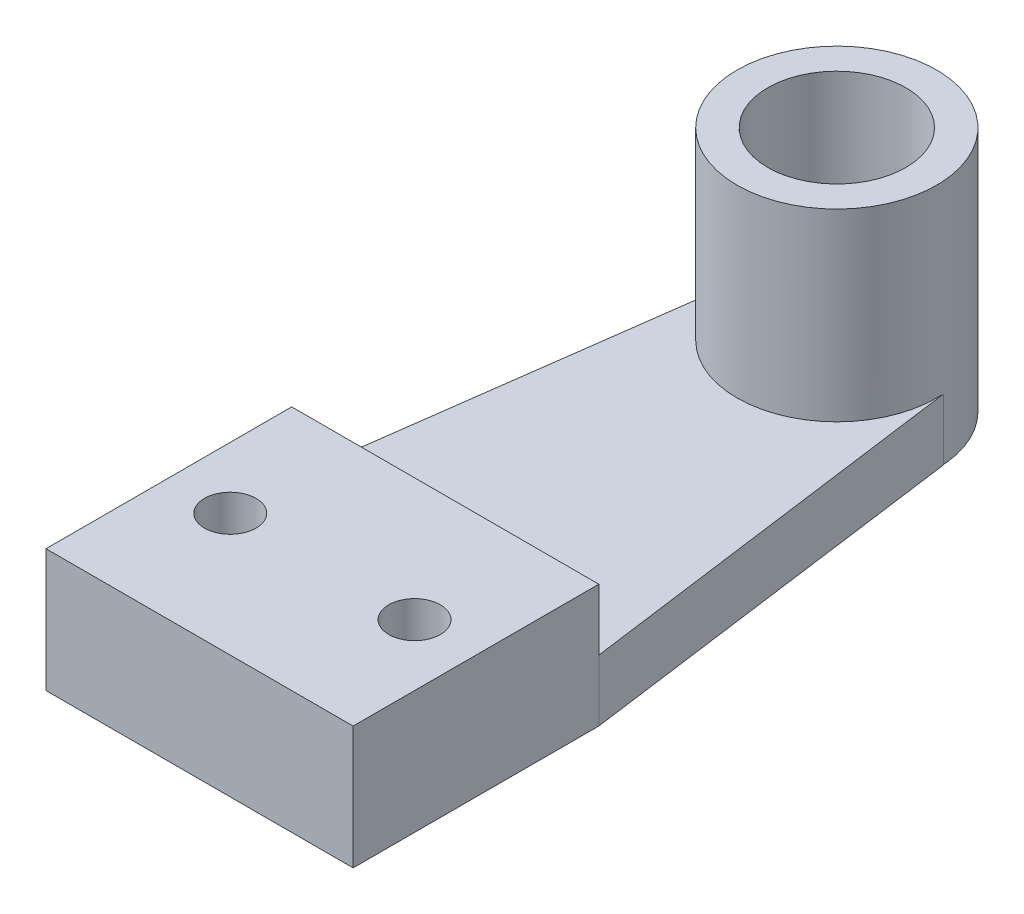
SolidWorks part; units mm, degrees
ref_plane "Front Plane" through (0, 0, 0) normal (0, 0, 1) x (1, 0, 0)
ref_plane "Top Plane" through (0, 0, 0) normal (0, 1, 0) x (1, 0, 0)
ref_plane "Right Plane" through (0, 0, 0) normal (1, 0, 0) x (0, 0, -1)
sketch "Sketch1" plane through (0, 0, 0) normal (0, 1, 0) x (1, 0, 0)
  line L0 (-12.5, 10) -> (-8.052, 42.9616)
  line L1 (-12.5, -10) -> (12.5, -10)
  line L2 (-12.5, -10) -> (-12.5, 10)
  line L3 (-12.5, 10) -> (12.5, 10)
  line L4 (12.5, -10) -> (12.5, 10)
  line L5 (-12.5, -10) -> (12.5, 10) construction
  line L6 (-12.5, 10) -> (12.5, -10) construction
  line L7 (-8.125, 10) -> (8.125, 10)
  line L8 (-8.125, 10) -> (-8.125, 50)
  line L9 (-8.125, 50) -> (8.125, 50)
  line L10 (8.125, 10) -> (8.125, 50)
  line L11 (-8.125, 10) -> (8.125, 50) construction
  line L12 (-8.125, 50) -> (8.125, 10) construction
  line L13 (12.5, 10) -> (8.052, 42.9616)
  circle A1 centre (0, 41.875) radius 8.125
  circle A2 centre (0, 41.875) radius 5.625
  circle A3 centre (-7.5, 0) radius 2.1
  circle A4 centre (7.5, 0) radius 2.1
  point P0 (0, 0)
  point P10 (0, 30)
  dimension "D3" = 11.25
  dimension "D4" = 2.5
  dimension "D5" = 4.2
  dimension "D1" = 40
  dimension "D2" = 20
  dimension "D6" = 15
  dimension "D7" = 25
  dimension "D8" = 7.5
extrude "Boss-Extrude1" add sketch "Sketch1" along normal blind 5 contours L1 L4 L3 L2 A4 A3 | A1 A2 | A1 L8 L3 L10 | A2 | L3 L8 L0 | L3 L13 L10 region at (0, 0, 0) region at (-9.5833, 0, -20.8069) region at (0, 0, -22.8113) region at (-5.1961, 0, -47.8193) region at (9.5833, 0, -20.8069) region at (0, 0, -41.875)
extrude "Boss-Extrude2" add sketch "Sketch1<3>" along normal blind 10 contours L1 L4 L3 L2 A4 A3 region at (0, 0, 0)
sketch "Sketch1<3>" plane through (0, 0, 0) normal (0, 1, 0) x (1, 0, 0) same geometry as "Sketch1"
extrude "Boss-Extrude3" add sketch "Sketch1<4>" along normal blind 20 contours A1 A2 region at (-5.1961, 0, -47.8193)
sketch "Sketch1<4>" plane through (0, 0, 0) normal (0, 1, 0) x (1, 0, 0) same geometry as "Sketch1"
equation "\"m3 hole\"= 3.2"
equation "\"m4 hole\"= 4.2"
equation "\"m5 hole\"= 5.2"
equation "\"m6 hole\"= 6.2"
equation "\"m8 hole\"= 8.2"
equation "\"m3 tapped\"= 2.5"
equation "\"m4 tapped\"= 3.3"
equation "\"m5 tapped\"= 4.2"
equation "\"m6 tapped\"= 5"
equation "\"m8 tapped\"= 6.8"
